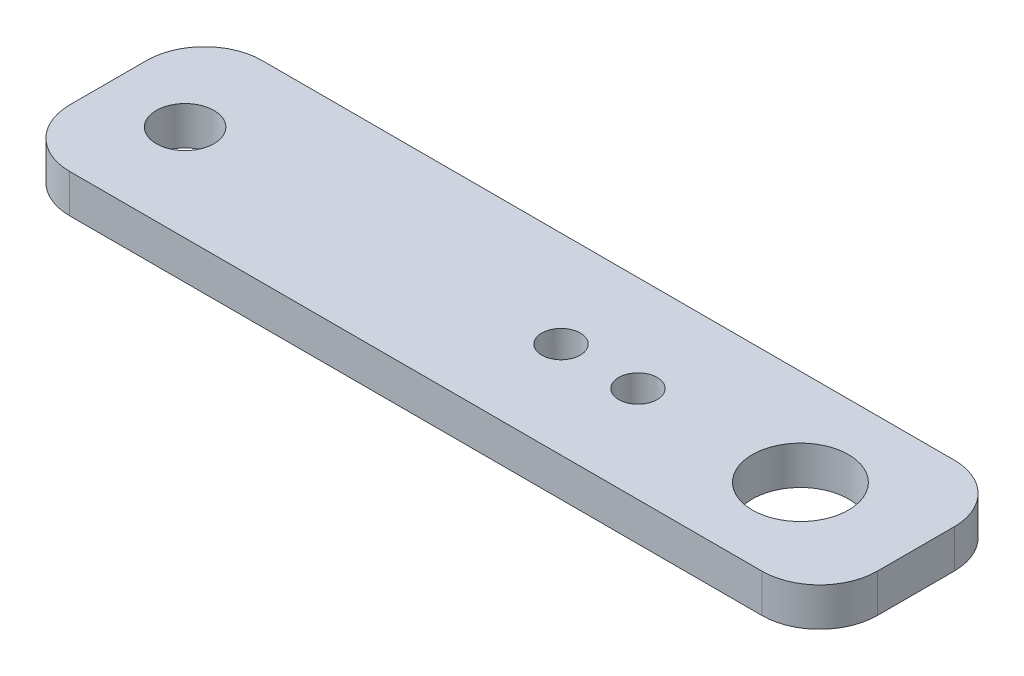
SolidWorks part; units mm, degrees
ref_plane "Front Plane" through (0, 0, 0) normal (0, 0, 1) x (1, 0, 0)
ref_plane "Top Plane" through (0, 0, 0) normal (0, 1, 0) x (1, 0, 0)
ref_plane "Right Plane" through (0, 0, 0) normal (1, 0, 0) x (0, 0, -1)
sketch "Sketch1" plane through (0, 0, 0) normal (0, 1, 0) x (1, 0, 0)
  line L1 (-21, 5) -> (21, 5)
  line L2 (-21, 5) -> (-21, -5)
  line L3 (-21, -5) -> (21, -5)
  line L4 (21, 5) -> (21, -5)
  line L5 (-21, 5) -> (21, -5) construction
  line L6 (-21, -5) -> (21, 5) construction
  point P0 (0, 0)
  dimension "D1" = 10
  dimension "D2" = 42
extrude "Boss-Extrude1" add sketch "Sketch1" along normal blind 2
hole_wizard "Ø5.0mm Dowel Hole1" positions "Sketch5" profile "Sketch6" hole size "Ø5.0" standard "ISO" end condition through all
sketch "Sketch5" plane through (0, 2, 0) normal (0, 1, 0) x (1, 0, 0)
  line L0 (21, -5) -> (21, 5) construction
  point P0 (15, 0)
  point P1 (0, 0)
  dimension "D1" = 6
sketch "Sketch6" plane through (15, 2, 0) normal (1, 0, 0) x (0, 0, 1)
  line L0 (0, 0) -> (0, 2)
  line L1 (0, 2) -> (2.5, 2)
  line L2 (2.5, 2) -> (2.5, 0)
  line L5 (2.5, 0) -> (0, 0)
  line L11 (0, -6.35) -> (0, 107.95) construction
  dimension "Thru Hole Dia." = 5
  dimension "Thru Hole Depth" = 2
hole_wizard "Ø3.0mm Dowel Hole1" positions "Sketch3" profile "Sketch4" hole size "Ø3.0" standard "ISO" end condition through all
sketch "Sketch3" plane through (0, 2, 0) normal (0, 1, 0) x (1, 0, 0)
  line L0 (-21, 5) -> (-21, -5) construction
  point P0 (-17, 0)
  dimension "D1" = 4
sketch "Sketch4" plane through (-17, 2, 0) normal (1, 0, 0) x (0, 0, 1)
  line L0 (0, 0) -> (0, 2)
  line L1 (0, 2) -> (1.5, 2)
  line L2 (1.5, 2) -> (1.5, 0)
  line L5 (1.5, 0) -> (0, 0)
  line L11 (0, -6.35) -> (0, 107.95) construction
  dimension "Thru Hole Dia." = 3
  dimension "Thru Hole Depth" = 2
sketch "Sketch2" plane through (0, 2, 0) normal (0, 1, 0) x (1, 0, 0)
  line L0 (15, 5) -> (15, -5) construction
  line L1 (-21, -5) -> (21, -5) construction
  line L3 (21, 0) -> (-21, 0) construction
  line L4 (21, -5) -> (21, 5) construction
  line L5 (-21, 5) -> (-21, -5) construction
  circle A3 centre (6.55, 0) radius 1
  circle A4 centre (2.55, 0) radius 1
  point P10 (15, 0)
  dimension "D1" = 2
  dimension "D2" = 8.45
  dimension "D3" = 4
extrude "Cut-Extrude1" cut sketch "Sketch2" against normal blind 3
fillet "Fillet1" radius 3 4 edges at (21, 1, 5) (21, 1, -5) (-21, 1, -5) (-21, 1, 5)
equation "\"globalength1\"=55"
